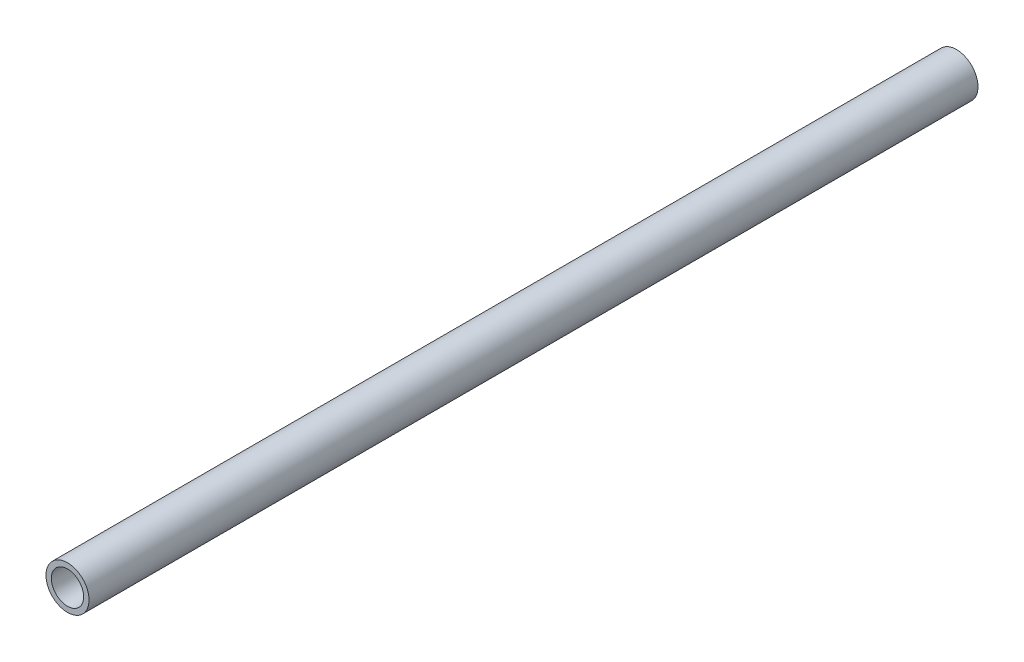
SolidWorks part; units mm, degrees
ref_plane "Front Plane" through (0, 0, 0) normal (0, 0, 1) x (1, 0, 0)
ref_plane "Top Plane" through (0, 0, 0) normal (0, 1, 0) x (1, 0, 0)
ref_plane "Right Plane" through (0, 0, 0) normal (1, 0, 0) x (0, 0, -1)
sketch "Sketch2" plane through (0, 0, 0) normal (0, 0, 1) x (1, 0, 0)
  circle A0 centre (0, 0) radius 40
  circle A1 centre (0, 0) radius 30
  dimension "D1" = 80
  dimension "D2" = 10
extrude "Boss-Extrude1" add sketch "Sketch2" along normal blind 1651 contours A0 A1 region at (-38.8686, 0, 0)
ref_axis "Axis1" through (0, 0, 1651) along (0, 0, -1)
